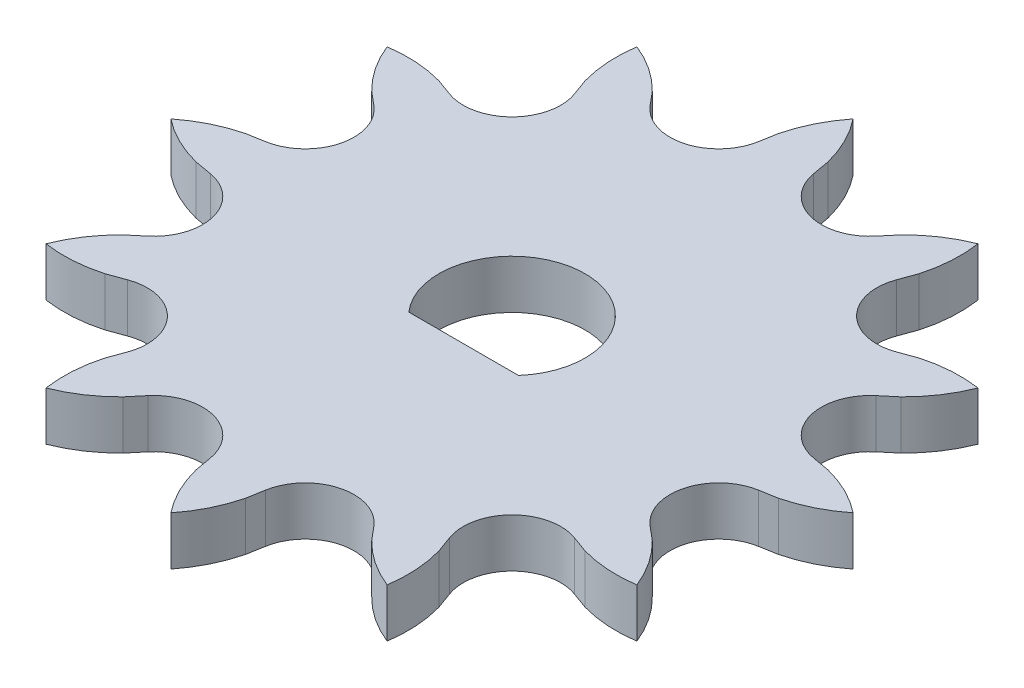
SolidWorks part; units mm, degrees
note: The reader was unsure of these and kept them because the rebuilt part matched: shared geometry of "Sketch2<5>".
ref_plane "Front Plane" through (0, 0, 0) normal (0, 0, 1) x (1, 0, 0)
ref_plane "Top Plane" through (0, 0, 0) normal (0, 1, 0) x (1, 0, 0)
ref_plane "Right Plane" through (0, 0, 0) normal (1, 0, 0) x (0, 0, -1)
sketch "Sketch1" plane through (0, 0, 0) normal (0, 1, 0) x (1, 0, 0)
  line L0 (0, 0) -> (0, 14) construction
  line L1 (0, 0) -> (-14, 0) construction
  line L2 (0, 0) -> (3.0919, 11.5948) construction
  line L3 (0, 0) -> (-3.0919, 11.5948) construction
  line L4 (-4.627, 10.313) -> (-5.0898, 10.8671)
  line L7 (-1.1222, 11.2475) -> (-0.9969, 11.9585)
  circle A0 centre (0, 0) radius 14
  circle A1 centre (0, 0) radius 10
  circle A2 centre (0, 0) radius 12 construction
  circle A3 centre (0, 0) radius 11.5 construction
  arc A6 (-4.627, 10.313) -> (-1.1222, 11.2475) centre (-3.0919, 11.5948) ccw
  conic Q0 (-0.9969, 11.9585) -> (0, 14) control (-0.371, 14) rho 0.627845
  conic Q1 (-5.0898, 10.8671) -> (-6.9708, 12.1412) control (-6.649, 12.3259) rho 0.627845
  dimension "D1" = 28
  dimension "D2" = 20
  dimension "D3" = 24
  dimension "D4" = 23
extrude "Boss-Extrude3" add sketch "Sketch1" along normal blind 2 contours L4 Q1 A0 Q0 L7 A6 A1 | A1 | Q1 L4 A6 L7 Q0 A0
sketch "Sketch2" plane through (0, 2, 0) normal (0, 1, 0) x (1, 0, 0)
  line L0 (0, 0) -> (0, 14) construction
  line L1 (0, 0) -> (3.6235, 13.523) construction
  line L2 (0, 0) -> (-3.6235, 13.523) construction
  line L3 (-1.0104, 11.9574) -> (-1.1362, 11.2438)
  line L4 (5.1037, 10.8606) -> (4.6379, 10.3055)
  line L5 (-1.881, 7.02) -> (-1.8257, 6.954)
  line L6 (-1.881, 7.02) -> (-1.8959, 6.9352)
  line L7 (-5.1037, 10.8606) -> (-4.6379, 10.3055)
  line L8 (1.0104, 11.9574) -> (1.1362, 11.2438)
  line L9 (9.8502, 6.8537) -> (9.1693, 6.6059)
  line L10 (6.8537, 9.8502) -> (6.6059, 9.1693)
  line L11 (11.9574, 1.0104) -> (11.2438, 1.1362)
  line L12 (10.8606, 5.1037) -> (10.3055, 4.6379)
  line L13 (10.8606, -5.1037) -> (10.3055, -4.6379)
  line L14 (11.9574, -1.0104) -> (11.2438, -1.1362)
  line L15 (6.8537, -9.8502) -> (6.6059, -9.1693)
  line L16 (9.8502, -6.8537) -> (9.1693, -6.6059)
  line L17 (1.0104, -11.9574) -> (1.1362, -11.2438)
  line L18 (5.1037, -10.8606) -> (4.6379, -10.3055)
  line L19 (-5.1037, -10.8606) -> (-4.6379, -10.3055)
  line L20 (-1.0104, -11.9574) -> (-1.1362, -11.2438)
  line L21 (-9.8502, -6.8537) -> (-9.1693, -6.6059)
  line L22 (-6.8537, -9.8502) -> (-6.6059, -9.1693)
  line L23 (-11.9574, -1.0104) -> (-11.2438, -1.1362)
  line L24 (-10.8606, -5.1037) -> (-10.3055, -4.6379)
  line L25 (-10.8606, 5.1037) -> (-10.3055, 4.6379)
  line L26 (-11.9574, 1.0104) -> (-11.2438, 1.1362)
  line L27 (-6.8537, 9.8502) -> (-6.6059, 9.1693)
  line L28 (-9.8502, 6.8537) -> (-9.1693, 6.6059)
  line L29 (0, 0) -> (-1.1362, 11.2438) construction
  circle A1 centre (0, 0) radius 11.5 construction
  circle A2 centre (0, 0) radius 10 construction
  circle A3 centre (0, 0) radius 12 construction
  arc A6 (-1.0104, 11.9574) -> (0, 14) centre (4.2499, 10.6266) cw
  arc A7 (-1.1362, 11.2438) -> (-4.6379, 10.3055) centre (-3.1058, 11.5911) cw
  arc A8 (-5.1037, 10.8606) -> (-7, 12.1244) centre (-8.9938, 7.078) ccw
  arc A10 (4.6379, 10.3055) -> (1.1362, 11.2438) centre (3.1058, 11.5911) cw
  arc A11 (5.1037, 10.8606) -> (7, 12.1244) centre (8.9938, 7.078) cw
  arc A12 (1.0104, 11.9574) -> (0, 14) centre (-4.2499, 10.6266) ccw
  arc A13 (9.1693, 6.6059) -> (6.6059, 9.1693) centre (8.4853, 8.4853) cw
  arc A14 (9.8502, 6.8537) -> (12.1244, 7) centre (11.3278, 1.6328) cw
  arc A15 (6.8537, 9.8502) -> (7, 12.1244) centre (1.6328, 11.3278) ccw
  arc A16 (11.2438, 1.1362) -> (10.3055, 4.6379) centre (11.5911, 3.1058) cw
  arc A17 (11.9574, 1.0104) -> (14, 0) centre (10.6266, -4.2499) cw
  arc A18 (10.8606, 5.1037) -> (12.1244, 7) centre (7.078, 8.9938) ccw
  arc A19 (10.3055, -4.6379) -> (11.2438, -1.1362) centre (11.5911, -3.1058) cw
  arc A20 (10.8606, -5.1037) -> (12.1244, -7) centre (7.078, -8.9938) cw
  arc A21 (11.9574, -1.0104) -> (14, 0) centre (10.6266, 4.2499) ccw
  arc A22 (6.6059, -9.1693) -> (9.1693, -6.6059) centre (8.4853, -8.4853) cw
  arc A23 (6.8537, -9.8502) -> (7, -12.1244) centre (1.6328, -11.3278) cw
  arc A24 (9.8502, -6.8537) -> (12.1244, -7) centre (11.3278, -1.6328) ccw
  arc A25 (1.1362, -11.2438) -> (4.6379, -10.3055) centre (3.1058, -11.5911) cw
  arc A26 (1.0104, -11.9574) -> (0, -14) centre (-4.2499, -10.6266) cw
  arc A27 (5.1037, -10.8606) -> (7, -12.1244) centre (8.9938, -7.078) ccw
  arc A28 (-4.6379, -10.3055) -> (-1.1362, -11.2438) centre (-3.1058, -11.5911) cw
  arc A29 (-5.1037, -10.8606) -> (-7, -12.1244) centre (-8.9938, -7.078) cw
  arc A30 (-1.0104, -11.9574) -> (0, -14) centre (4.2499, -10.6266) ccw
  arc A31 (-9.1693, -6.6059) -> (-6.6059, -9.1693) centre (-8.4853, -8.4853) cw
  arc A32 (-9.8502, -6.8537) -> (-12.1244, -7) centre (-11.3278, -1.6328) cw
  arc A33 (-6.8537, -9.8502) -> (-7, -12.1244) centre (-1.6328, -11.3278) ccw
  arc A34 (-11.2438, -1.1362) -> (-10.3055, -4.6379) centre (-11.5911, -3.1058) cw
  arc A35 (-11.9574, -1.0104) -> (-14, 0) centre (-10.6266, 4.2499) cw
  arc A36 (-10.8606, -5.1037) -> (-12.1244, -7) centre (-7.078, -8.9938) ccw
  arc A37 (-10.3055, 4.6379) -> (-11.2438, 1.1362) centre (-11.5911, 3.1058) cw
  arc A38 (-10.8606, 5.1037) -> (-12.1244, 7) centre (-7.078, 8.9938) cw
  arc A39 (-11.9574, 1.0104) -> (-14, 0) centre (-10.6266, -4.2499) ccw
  arc A40 (-6.6059, 9.1693) -> (-9.1693, 6.6059) centre (-8.4853, 8.4853) cw
  arc A41 (-6.8537, 9.8502) -> (-7, 12.1244) centre (-1.6328, 11.3278) cw
  arc A42 (-9.8502, 6.8537) -> (-12.1244, 7) centre (-11.3278, 1.6328) ccw
  dimension "D2" = 20
  dimension "D3" = 23
  dimension "D4" = 24
  dimension "D5" = 15
  dimension "D7" = 11.3011
  dimension "D6" = 15
  dimension "D8" = 10
extrude "Cut-Extrude4" cut sketch "Sketch2" against normal blind 2
sketch "Sketch3" plane through (0, 2, 0) normal (0, 1, 0) x (1, 0, 0)
  line L0 (-2.25, -1.9843) -> (2.25, -1.9843)
  arc A0 (2.25, -1.9843) -> (-2.25, -1.9843) centre (0, 0) ccw
  dimension "D1" = 6
  dimension "D2" = 4.5
extrude "Cut-Extrude5" cut sketch "Sketch3" against normal blind 2
sketch "Sketch4" plane through (0, 2, 0) normal (0, 1, 0) x (1, 0, 0)
  point P0 (0, 0)
extrude "Cut-Extrude7" cut sketch "Sketch2<5>" against normal blind 2 contours A42 L28 A40 L27 A41 L5 | A39 L26 A37 L25 A38 L5 | A36 L24 A34 L23 A35 L5 | A33 L22 A31 L21 A32 L5 | A30 L20 A28 L19 A29 L5 | A27 L18 A25 L17 A26 L5 | A24 L16 A22 L15 A23 L5 | A21 L14 A19 L13 A20 L5 | A18 L12 A16 L11 A17 L5 | A15 L10 A13 L9 A14 L5 | A12 L8 A10 L4 A11 L5
sketch "Sketch2<5>" plane through (0, 2, 0) normal (0, 1, 0) x (1, 0, 0) same geometry as "Sketch2"
